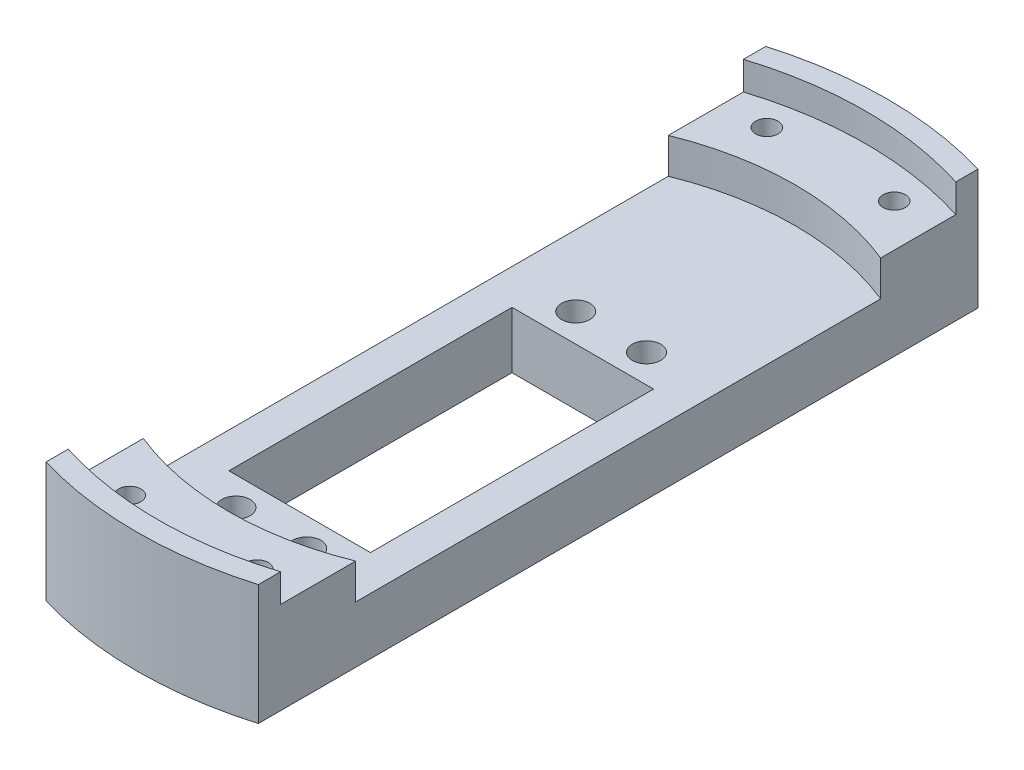
SolidWorks part; units mm, degrees
material "ABS"
ref_plane "Спереди" through (0, 0, 0) normal (0, 0, 1) x (1, 0, 0)
ref_plane "Сверху" through (0, 0, 0) normal (0, 1, 0) x (1, 0, 0)
ref_plane "Справа" through (0, 0, 0) normal (1, 0, 0) x (0, 0, -1)
sketch "Эскиз1" plane through (0, 0, 0) normal (0, 1, 0) x (1, 0, 0)
  line L0 (0, 0) -> (0, -69.818) construction
  line L1 (-1000, -10) -> (49000, -10) construction
  line L2 (-10, -30) -> (10, -30)
  line L3 (-10, -30) -> (-10, 10)
  line L4 (-10, 10) -> (10, 10)
  line L5 (10, -30) -> (10, 10)
  line L6 (-10, -30) -> (10, 10) construction
  line L7 (-10, 10) -> (10, -30) construction
  line L8 (-1000, 0) -> (49000, 0) construction
  line L9 (-15, -50.8331) -> (-15, 50.8331)
  line L10 (15, -50.8331) -> (15, 50.8331)
  arc A0 (-15, -50.8331) -> (15, -50.8331) centre (0, 0) ccw
  circle A1 centre (-5, -34) radius 2
  circle A2 centre (5, -34) radius 2
  circle A3 centre (5, 14) radius 2
  circle A4 centre (-5, 14) radius 2
  arc A5 (15, 50.8331) -> (-15, 50.8331) centre (0, 0) ccw
  point P3 (0, -10)
  dimension "D1" = 53
  dimension "D5" = 4
  dimension "D10" = 53
  dimension "D2" = 10
  dimension "D3" = 40
  dimension "D4" = 20
  dimension "D6" = 24
  dimension "D7" = 5
  dimension "D8" = 15
  dimension "D9" = 15
extrude "Бобышка-Вытянуть1" add sketch "Эскиз1" along normal blind 8
sketch "Эскиз2" plane through (0, 8, 0) normal (0, 1, 0) x (1, 0, 0)
  line L0 (-15, 37.081) -> (-15, 50.8331)
  line L1 (-15, 50.8331) -> (-15, -50.8331) construction
  line L2 (15, 50.8331) -> (15, 37.081)
  line L3 (15, -50.8331) -> (15, 50.8331) construction
  line L4 (-15, -37.081) -> (-15, -50.8331)
  line L5 (15, -37.081) -> (15, -50.8331)
  arc A0 (-15, -50.8331) -> (15, -50.8331) centre (0, 0) ccw
  arc A1 (-15, -37.081) -> (15, -37.081) centre (0, 0) ccw
  arc A2 (15, 37.081) -> (-15, 37.081) centre (0, 0) ccw
  arc A3 (15, 50.8331) -> (-15, 50.8331) centre (0, 0) ccw
  dimension "D1" = 30
  dimension "D2" = 80
  dimension "D3" = 53
extrude "Бобышка-Вытянуть2" add sketch "Эскиз2" along normal blind 5
hole_wizard "Сверло под метчик  спиральное M31" positions "Эскиз6" profile "Эскиз7" hole size "M3x0.5" standard "DIN" end condition through all
sketch "Эскиз6" plane through (0, 13, 0) normal (0, 1, 0) x (1, 0, 0)
  point P0 (-9, -45)
  dimension "D1" = 9
  dimension "D2" = 45
sketch "Эскиз7" plane through (-9, 13, 45) normal (1, 0, 0) x (0, 0, 1)
  line L0 (0, 0) -> (0, 13)
  line L1 (0, 13) -> (1.575, 13)
  line L2 (1.575, 13) -> (1.575, 0)
  line L5 (1.575, 0) -> (0, 0)
  line L11 (0, -6.35) -> (0, 107.95) construction
  dimension "Диаметр сквозного отверстия" = 3.15
  dimension "Глубина сквозного отверстия" = 13
sketch "Эскиз8" plane through (0, 0, 0) normal (0, 1, 0) x (1, 0, 0)
  line L0 (0, 0) -> (33.0205, 0) construction
  line L1 (0, 0) -> (0, -18.8534) construction
pattern_linear "Линейный массив1" count 2 spacing 18 along (1, 0, 0) count 2 spacing 90 along (0, 0, -1) of "Сверло под метчик  спиральное M31"
sketch "Эскиз9" plane through (0, 13, 0) normal (0, 1, 0) x (1, 0, 0)
  line L0 (-15, 50.8331) -> (-15, 47.697)
  line L3 (15, 50.8331) -> (15, 47.697)
  line L4 (15, 37.081) -> (15, 50.8331) construction
  line L5 (-15, -50.8331) -> (-15, -47.697)
  line L6 (15, -50.8331) -> (15, -47.697)
  arc A0 (-15, -50.8331) -> (15, -50.8331) centre (0, 0) ccw
  arc A1 (-15, -47.697) -> (15, -47.697) centre (0, 0) ccw
  arc A2 (15, 47.697) -> (-15, 47.697) centre (0, 0) ccw
  arc A3 (15, 50.8331) -> (-15, 50.8331) centre (0, 0) ccw
  dimension "D1" = 53
  dimension "D2" = 100
  dimension "D3" = 30
extrude "Бобышка-Вытянуть3" add sketch "Эскиз9" along normal blind 4
